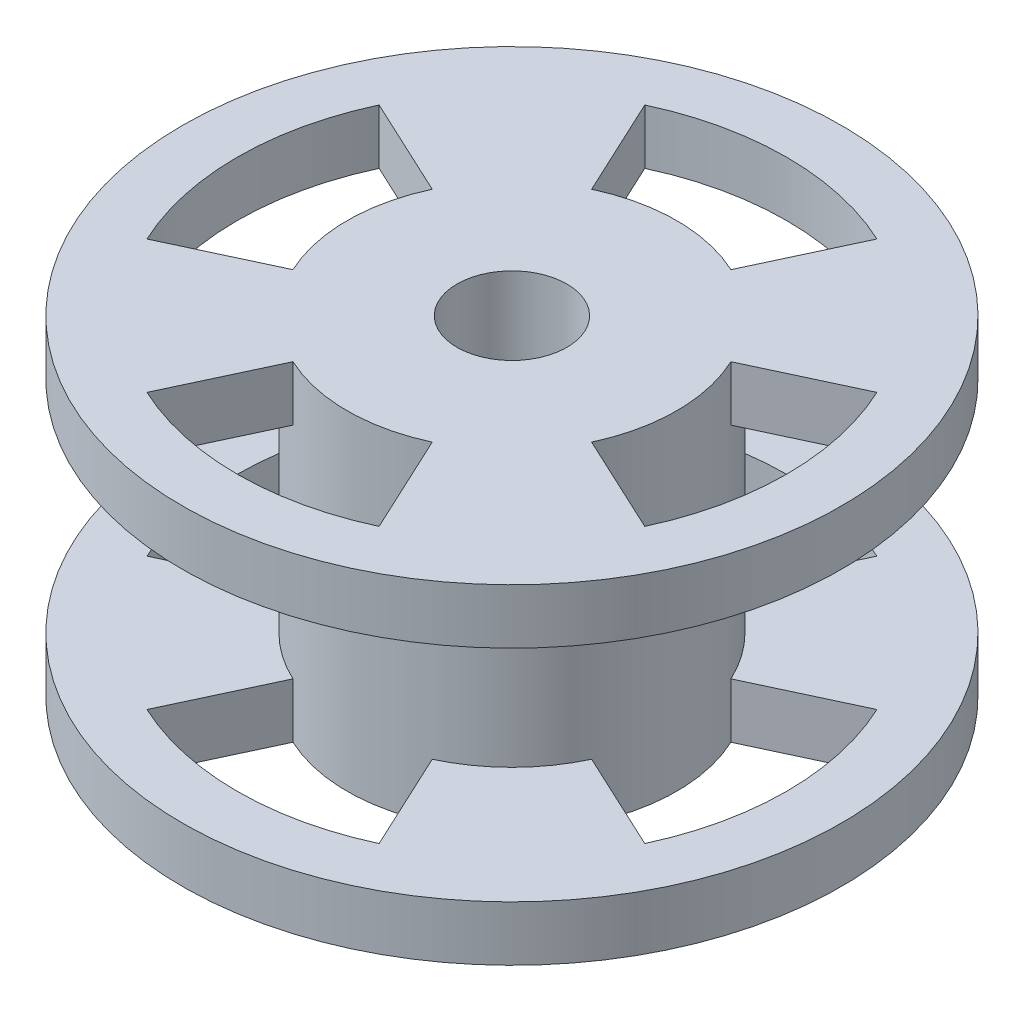
SolidWorks part; units mm, degrees
ref_plane "Front Plane" through (0, 0, 0) normal (0, 0, 1) x (1, 0, 0)
ref_plane "Top Plane" through (0, 0, 0) normal (0, 1, 0) x (1, 0, 0)
ref_plane "Right Plane" through (0, 0, 0) normal (1, 0, 0) x (0, 0, -1)
sketch "Sketch1" plane through (0, 0, 0) normal (0, 0, 1) x (1, 0, 0)
  line L0 (0, 0) -> (0, 7.5)
  line L1 (0, 7.5) -> (5, 7.5) construction
  line L2 (5, 7.5) -> (5, 2.5)
  line L3 (5, 2.5) -> (12.5, 2.5)
  line L4 (12.5, 2.5) -> (12.5, 0)
  line L5 (12.5, 0) -> (0, 0)
  line L6 (0, 7.5) -> (0, 15)
  line L7 (0, 15) -> (12.5, 15)
  line L8 (12.5, 15) -> (12.5, 12.5)
  line L9 (12.5, 12.5) -> (5, 12.5)
  line L10 (5, 12.5) -> (5, 7.5)
  line L11 (-2.5, 15) -> (-2.5, 0) construction
  line L12 (0, 15) -> (-2.5, 15) construction
  line L13 (0, 0) -> (-2.5, 0) construction
  dimension "D1" = 2.5
  dimension "D2" = 7.5
  dimension "D3" = 12.5
  dimension "D4" = 5
  dimension "D5" = 2.5
revolve "Revolve2" add sketch "Sketch1" angle 360 about L11
sketch "Sketch3" plane through (0, 15, 0) normal (0, 1, 0) x (1, 0, 0)
  line L0 (-2.5, 15) -> (-2.5, -15) construction
  line L1 (-17.5, 0) -> (12.5, 0) construction
  line L2 (-2.5, 0) -> (-7.7827, 11.3288) construction
  line L3 (-7.7827, 11.3288) -> (-5.6696, 6.7973)
  line L4 (2.7827, 11.3288) -> (0.6696, 6.7973)
  line L5 (8.8288, -5.2827) -> (4.2973, -3.1696)
  line L6 (8.8288, 5.2827) -> (4.2973, 3.1696)
  line L7 (-7.7827, -11.3288) -> (-5.6696, -6.7973)
  line L8 (2.7827, -11.3288) -> (0.6696, -6.7973)
  line L9 (-13.8288, 5.2827) -> (-9.2973, 3.1696)
  line L10 (-13.8288, -5.2827) -> (-9.2973, -3.1696)
  circle A0 centre (-2.5, 0) radius 7.5 construction
  circle A1 centre (-2.5, 0) radius 7.5 construction
  arc A2 (4.2973, 3.1696) -> (4.2973, -3.1696) centre (-2.5, 0) cw
  circle A3 centre (-2.5, 0) radius 15 construction
  circle A4 centre (-2.5, 0) radius 12.5
  circle A5 centre (-2.5, 0) radius 12.5 construction
  arc A6 (-7.7827, 11.3288) -> (2.7827, 11.3288) centre (-2.5, 0) cw
  arc A7 (-5.6696, 6.7973) -> (0.6696, 6.7973) centre (-2.5, 0) cw
  arc A8 (8.8288, 5.2827) -> (8.8288, -5.2827) centre (-2.5, 0) cw
  arc A9 (0.6696, -6.7973) -> (-5.6696, -6.7973) centre (-2.5, 0) cw
  arc A10 (2.7827, -11.3288) -> (-7.7827, -11.3288) centre (-2.5, 0) cw
  arc A11 (-9.2973, -3.1696) -> (-9.2973, 3.1696) centre (-2.5, 0) cw
  arc A12 (-13.8288, -5.2827) -> (-13.8288, 5.2827) centre (-2.5, 0) cw
  point P34 (-2.5, 0)
  dimension "D2" = 25
  dimension "D1" = 2.5
  dimension "D3" = 4
extrude "Cut-Extrude1" cut sketch "Sketch3" against normal through all
